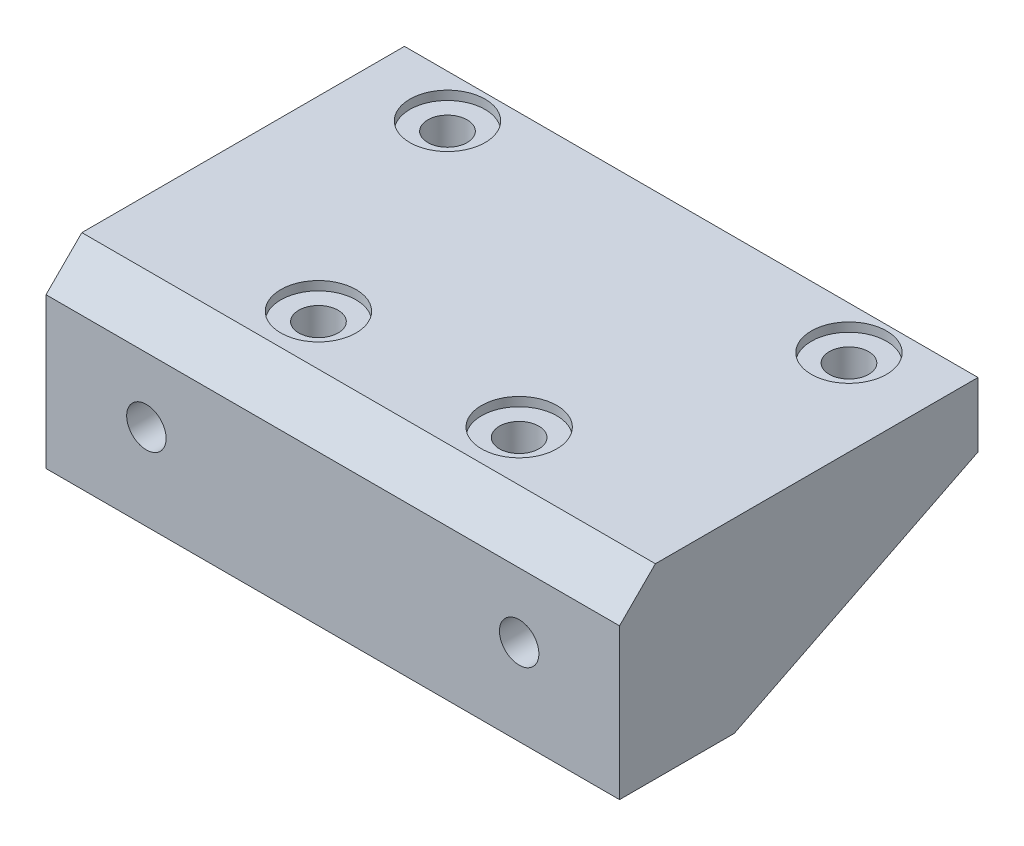
SolidWorks part; units mm, degrees
material "6061-T6 (SS)"
ref_plane "Front Plane" through (0, 0, 0) normal (0, 0, 1) x (1, 0, 0)
ref_plane "Top Plane" through (0, 0, 0) normal (0, 1, 0) x (1, 0, 0)
ref_plane "Right Plane" through (0, 0, 0) normal (1, 0, 0) x (0, 0, -1)
sketch "Sketch1" plane through (0, 0, 0) normal (0, 0, 1) x (1, 0, 0)
  line L1 (0, 0) -> (68, 0)
  line L2 (0, 0) -> (0, 26)
  line L3 (0, 26) -> (68, 26)
  line L4 (68, 0) -> (68, 26)
  dimension "D1" = 68
  dimension "D2" = 26
extrude "Boss-Extrude1" add sketch "Sketch1" along normal blind 6
sketch "Sketch2" plane through (0, 0, 6) normal (0, 0, 1) x (1, 0, 0)
  line L0 (68, 26) -> (0, 26) construction
  line L1 (-6, 26) -> (74, 26)
  line L2 (-6, 26) -> (-6, 20)
  line L3 (-6, 20) -> (74, 20)
  line L4 (74, 26) -> (74, 20)
  line L5 (34, 0) -> (34, 20) construction
  line L6 (0, 0) -> (68, 0) construction
  dimension "D1" = 6
  dimension "D2" = 80
extrude "Boss-Extrude2" add sketch "Sketch2" against normal blind 50
sketch "Sketch3" plane through (0, 0, 0) normal (0, 0, -1) x (-1, 0, 0)
  line L0 (-68, 0) -> (-68, 20) construction
  line L1 (0, 20) -> (0, 0) construction
  line L2 (-60, 12) -> (-8, 12) construction
  line L4 (-68, 20) -> (0, 20) construction
  point P0 (-60, 12)
  point P2 (-8, 12)
  dimension "D1" = 8
  dimension "D2" = 8
  dimension "D3" = 8
hole_wizard "M5 Clearance Hole1" positions "Sketch3" profile "Sketch4" hole size "M5" standard "DIN"
sketch "Sketch4" plane through (60, 12, 0) normal (1, 0, 0) x (0, 1, 0)
  line L0 (0, 0) -> (0, 11.6524)
  line L1 (0, 11.6524) -> (2.75, 10)
  line L2 (2.75, 10) -> (2.75, 0)
  line L5 (2.75, 0) -> (0, 0)
  line L10 (0, 11.6524) -> (-2.75, 10) construction
  line L11 (0, -6.35) -> (0, 107.95) construction
  dimension "Hole Dia." = 5.5
  dimension "Hole Depth" = 10
  dimension "Drill Angle" = 118
sketch "Sketch5" plane through (74, 0, 0) normal (1, 0, 0) x (0, 0, -1)
  line L0 (-6, 0) -> (10, 0)
  line L2 (44, 20) -> (-6, 20)
  line L3 (-6, 20) -> (-6, 0)
  line L4 (44, 20) -> (44, 17)
  line L5 (44, 17) -> (10, 0)
  dimension "D1" = 16
  dimension "D2" = 3
extrude "Boss-Extrude3" add sketch "Sketch5" against normal up to surface (6 mm away) up to face at (68, 10, 3)
extrude "Boss-Extrude4" add sketch "Sketch5<2>" along normal up to surface (-74 mm away) from surface up to face at (0, 10, 3) starting at face at (-6, 23, -19)
sketch "Sketch5<2>" plane through (74, 0, 0) normal (1, 0, 0) x (0, 0, -1) same geometry as "Sketch5"
sketch "Sketch6" plane through (0, 20, 0) normal (0, -1, 0) x (-1, 0, 0)
  line L1 (0, 0) -> (0, 44) construction
  line L2 (-62, 38) -> (-6, 38) construction
  line L4 (0, 44) -> (-68, 44) construction
  line L5 (-20, 6) -> (-48, 6) construction
  line L7 (-34, 6) -> (-34, 0) construction
  line L8 (-68, 0) -> (0, 0) construction
  line L9 (-68, 10) -> (-68, 44) construction
  point P0 (-48, 6)
  point P2 (-20, 6)
  point P4 (-62, 38)
  point P6 (-6, 38)
  dimension "D2" = 6
  dimension "D3" = 6
  dimension "D4" = 28
  dimension "D5" = 6
  dimension "D1" = 6
hole_wizard "M5 Clearance Hole2" positions "Sketch6" profile "Sketch7" hole size "M5" standard "DIN"
sketch "Sketch7" plane through (48, 20, -6) normal (1, 0, 0) x (0, 0, -1)
  line L0 (0, 0) -> (0, 11.6524)
  line L1 (0, 11.6524) -> (2.75, 10)
  line L2 (2.75, 10) -> (2.75, 0)
  line L5 (2.75, 0) -> (0, 0)
  line L10 (0, 11.6524) -> (-2.75, 10) construction
  line L11 (0, -6.35) -> (0, 107.95) construction
  dimension "Hole Dia." = 5.5
  dimension "Hole Depth" = 10
  dimension "Drill Angle" = 118
ref_plane "Plane1" through (34, 0, 0) normal (-1, 0, 0) x (0, 0, 1)
sketch "Sketch9" plane through (34, 0, 0) normal (-1, 0, 0) x (0, 0, 1)
  line L0 (0, 0) -> (-44, 20)
  line L1 (0, 20) -> (-44, 20) construction
  line L2 (0, 20) -> (-44, 20) construction
  point P5 (0, 0)
rib "Rib1" sketch "Sketch9" sketch "Sketch9" thickness 12 extrusion direction parallel to sketch draft on no parameters "D1"=12
fillet "Fillet1" radius 2.5 2 edges at (68, 10, 0) (0, 10, 0)
fillet "Fillet2" radius 1 10 edges at (68, 20, -23.25) (67.2678, 20, -0.7322) (52.75, 20, 0) (15.25, 20, 0) (0.7322, 20, -0.7322) (0, 20, -23.25) (28, 20, -22) (28, 10, 0) (40, 10, 0) (40, 20, -22)
sketch "Sketch8" plane through (0, 26, 0) normal (0, 1, 0) x (1, 0, 0)
  circle A0 centre (6, 38) radius 5.25
  circle A1 centre (62, 38) radius 5.25
  circle A2 centre (48, 6) radius 5.25
  circle A3 centre (20, 6) radius 5.25
  dimension "D1" = 10.5
extrude "Cut-Extrude1" cut sketch "Sketch8" against normal blind 1.25
chamfer "Chamfer1" distance 5 angle 45 1 edges at (34, 26, 6)
equation "\"D2@Sketch3\"=\"D1@Sketch3\""
equation "\"D2@Sketch6\"=\"D1@Sketch6\""
